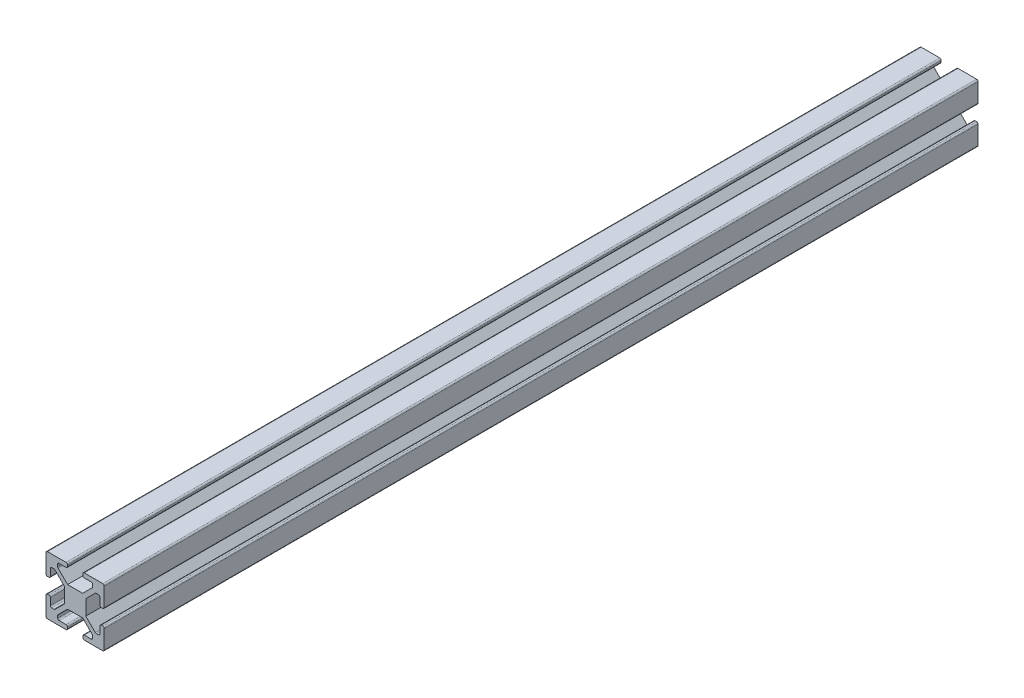
SolidWorks part; units mm, degrees
material "6061 Alloy"
ref_plane "Front Plane" through (0, 0, 0) normal (0, 0, 1) x (1, 0, 0)
ref_plane "Top Plane" through (0, 0, 0) normal (0, 1, 0) x (1, 0, 0)
ref_plane "Right Plane" through (0, 0, 0) normal (1, 0, 0) x (0, 0, -1)
sketch "Sketch1" plane through (0, 0, 0) normal (0, 0, 1) x (1, 0, 0)
  line L0 (-10, 2.63) -> (-10, 10)
  line L1 (-10, 10) -> (-2.63, 10)
  line L2 (-2.63, 10) -> (-2.63, 8.5)
  line L3 (-2.63, 8.5) -> (-5.995, 8.5)
  line L4 (-5.995, 8.5) -> (-5.995, 7.0557)
  line L5 (-5.995, 7.0557) -> (-2.5943, 3.655)
  line L6 (-2.5943, 3.655) -> (2.5943, 3.655)
  line L7 (0, 3.655) -> (0, 0) construction
  line L8 (0, 0) -> (-3.655, 0) construction
  line L9 (-3.655, -2.5943) -> (-3.655, 2.5943)
  line L10 (-3.655, 2.5943) -> (-7.0557, 5.995)
  line L11 (-7.0557, 5.995) -> (-8.5, 5.995)
  line L12 (-8.5, 5.995) -> (-8.5, 2.63)
  line L13 (-8.5, 2.63) -> (-10, 2.63)
  line L14 (8.5, 2.63) -> (10, 2.63)
  line L15 (8.5, 5.995) -> (8.5, 2.63)
  line L16 (7.0557, 5.995) -> (8.5, 5.995)
  line L17 (3.655, 2.5943) -> (7.0557, 5.995)
  line L18 (3.655, -2.5943) -> (3.655, 2.5943)
  line L19 (5.995, 7.0557) -> (2.5943, 3.655)
  line L20 (5.995, 8.5) -> (5.995, 7.0557)
  line L21 (2.63, 8.5) -> (5.995, 8.5)
  line L22 (2.63, 10) -> (2.63, 8.5)
  line L23 (10, 10) -> (2.63, 10)
  line L24 (10, 2.63) -> (10, 10)
  line L25 (10, -2.63) -> (10, -10)
  line L26 (10, -10) -> (2.63, -10)
  line L27 (2.63, -10) -> (2.63, -8.5)
  line L28 (2.63, -8.5) -> (5.995, -8.5)
  line L29 (5.995, -8.5) -> (5.995, -7.0557)
  line L30 (5.995, -7.0557) -> (2.5943, -3.655)
  line L31 (3.655, -2.5943) -> (7.0557, -5.995)
  line L32 (7.0557, -5.995) -> (8.5, -5.995)
  line L33 (8.5, -5.995) -> (8.5, -2.63)
  line L34 (8.5, -2.63) -> (10, -2.63)
  line L35 (-8.5, -2.63) -> (-10, -2.63)
  line L36 (-8.5, -5.995) -> (-8.5, -2.63)
  line L37 (-7.0557, -5.995) -> (-8.5, -5.995)
  line L38 (-3.655, -2.5943) -> (-7.0557, -5.995)
  line L39 (-2.5943, -3.655) -> (2.5943, -3.655)
  line L40 (-5.995, -7.0557) -> (-2.5943, -3.655)
  line L41 (-5.995, -8.5) -> (-5.995, -7.0557)
  line L42 (-2.63, -8.5) -> (-5.995, -8.5)
  line L43 (-2.63, -10) -> (-2.63, -8.5)
  line L44 (-10, -10) -> (-2.63, -10)
  line L45 (-10, -2.63) -> (-10, -10)
  point P41 (3.655, 0)
  dimension "D1" = 20
  dimension "D2" = 20
  dimension "D3" = 5.26
  dimension "D4" = 11.99
  dimension "D5" = 1.5
  dimension "D6" = 1.5
  dimension "D7" = 7.31
extrude "Boss-Extrude1" add sketch "Sketch1" against normal blind 300
fillet "Fillet1" radius 0.5 36 edges at (10, 10, -150) (7.0557, 5.995, -150) (8.5, 2.63, -150) (10, 2.63, -150) (8.5, 5.995, -150) (2.63, 10, -150) (2.63, 8.5, -150) (5.995, 8.5, -150) (5.995, 7.0557, -150) (10, -10, -150) (10, -2.63, -150) (8.5, -2.63, -150) (8.5, -5.995, -150) (7.0557, -5.995, -150) (5.995, -7.0557, -150) (5.995, -8.5, -150) (2.63, -8.5, -150) (2.63, -10, -150) (-10, -10, -150) (-2.63, -10, -150) (-2.63, -8.5, -150) (-5.995, -8.5, -150) (-5.995, -7.0557, -150) (-7.0557, -5.995, -150) (-8.5, -5.995, -150) (-10, -2.63, -150) (-8.5, -2.63, -150) (-7.0557, 5.995, -150) (-10, 10, -150) (-10, 2.63, -150) (-8.5, 2.63, -150) (-8.5, 5.995, -150) (-5.995, 8.5, -150) (-5.995, 7.0557, -150) (-2.63, 8.5, -150) (-2.63, 10, -150)
sketch "Sketch2" [suppressed] plane through (0, 0, 0) normal (1, 0, 0) x (0, 0, -1)
  line L0 (150, 9.5) -> (150, -9.5) construction
  line L1 (300, 9.5) -> (0, 9.5) construction
  line L2 (0, -9.5) -> (300, -9.5) construction
  line L3 (20, 4) -> (30, 4)
  line L4 (20, -4) -> (30, -4)
  line L5 (280, 4) -> (270, 4)
  line L6 (280, -4) -> (270, -4)
  arc A0 (20, 4) -> (20, -4) centre (20, 0) ccw
  arc A2 (30, -4) -> (30, 4) centre (30, 0) ccw
  arc A3 (280, 4) -> (280, -4) centre (280, 0) cw
  arc A4 (270, -4) -> (270, 4) centre (270, 0) cw
  dimension "D1" = 8
  dimension "D2" = 20
  dimension "D3" = 10
extrude "Cut-Extrude1" [suppressed] cut sketch "Sketch2" against normal through all both and the other way through all
